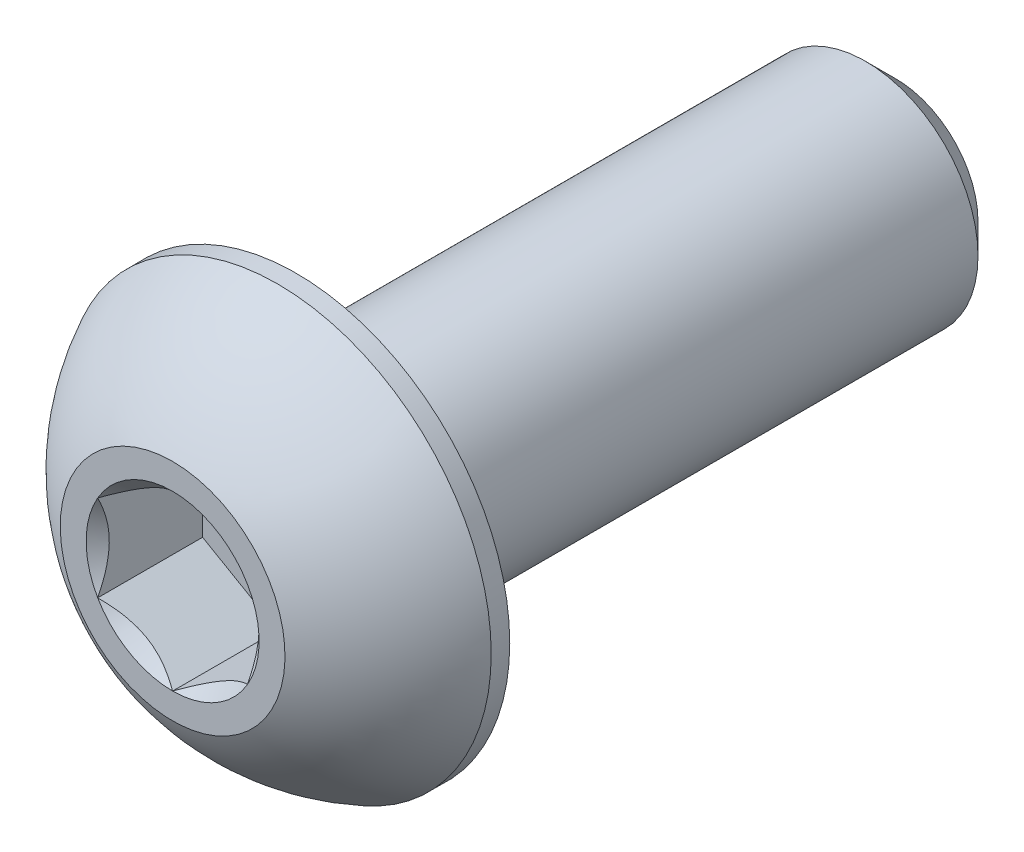
SolidWorks part; units mm, degrees
material "Alloy Steel"
ref_plane "Front Plane" through (0, 0, 0) normal (0, 0, 1) x (1, 0, 0)
ref_plane "Top Plane" through (0, 0, 0) normal (0, 1, 0) x (1, 0, 0)
ref_plane "Right Plane" through (0, 0, 0) normal (1, 0, 0) x (0, 0, -1)
sketch "Sketch1" plane through (0, 0, 0) normal (1, 0, 0) x (0, 0, -1)
  line L0 (-4.825, 0) -> (4.825, 0) construction
  line L1 (-3.175, 2.85) -> (-3.175, -2.85) construction
  line L2 (4.825, 1.5) -> (4.825, -1.5) construction
  line L3 (4.7937, 1.5541) -> (5.0437, 1.1211) construction
  line L4 (5.0437, 1.1211) -> (5.2938, 1.5541) construction
  line L5 (5.2938, 1.5541) -> (4.7937, 1.5541) construction
  line L6 (4.825, 1.5) -> (5.2625, 1.5) construction
  line L7 (5.0437, 1.5541) -> (5.0437, 1.5) construction
  line L8 (5.0437, 1.5) -> (5.0437, 1.1752) construction
  line L9 (5.0437, 1.1752) -> (5.0437, 1.1211) construction
  line L10 (5.0125, 1.1752) -> (5.075, 1.1752)
  line L11 (4.8094, 1.5271) -> (5.2781, 1.5271)
  line L12 (5.075, 1.1752) -> (5.2781, 1.5271)
  line L13 (5.0125, 1.1752) -> (4.8094, 1.5271)
  line L14 (-4.825, 1) -> (-4.825, -1) construction
  line L15 (4.825, 1.5) -> (-3.175, 1.5) construction
  point P3 (-3.175, 0)
  point P6 (-3.425, 0)
  point P21 (5.0437, 1.5271)
  point P24 (-3.4225, 2.85)
  point P25 (3.575, -1.5)
  point P26 (-4.825, 1.5)
  dimension "Head Height" = 1.65
  dimension "Length" = 8
  dimension "Head Dia" = 5.7
  dimension "Thread Dia" = 3
  dimension "Pitch" = 0.5
  dimension "D2" = 0.0625
  dimension "Drive Size" = 2
  dimension "D1" = 1.4
  dimension "D3" = 0.2475
  dimension "D4" = 1.25
sketch "Sketch2" plane through (0, 0, 0) normal (1, 0, 0) x (0, 0, -1)
  line L0 (-4.825, 0) -> (4.825, 0)
  line L1 (4.825, 0) -> (4.825, 1.1)
  line L2 (4.825, 1.5) -> (4.825, -1.5) construction
  line L3 (4.825, 1.1) -> (4.425, 1.5)
  line L4 (4.425, 1.5) -> (-3.175, 1.5)
  line L5 (-3.175, 2.85) -> (-3.175, -2.85) construction
  line L6 (-3.175, 1.5) -> (-3.175, 2.85)
  line L7 (-3.175, 2.85) -> (-3.4225, 2.85)
  line L8 (4.825, 1.5) -> (5.2625, 1.5) construction
  line L9 (-4.825, 0) -> (-4.825, 1.5)
  arc A0 (-4.825, 1.5) -> (-3.4225, 2.85) centre (-2.0302, 0) cw
  dimension "D1" = 0.4
  dimension "D2" = 45
revolve "Revolve1" add sketch "Sketch2" angle 360 about L0
sketch "Sketch3" plane through (0, 0, 4.825) normal (0, 0, 1) x (1, 0, 0)
  line L1 (0, 1.1547) -> (-1, 0.5774)
  line L2 (-1, 0.5774) -> (-1, -0.5774)
  line L3 (-1, -0.5774) -> (0, -1.1547)
  line L4 (0, -1.1547) -> (1, -0.5774)
  line L5 (1, -0.5774) -> (1, 0.5774)
  line L6 (1, 0.5774) -> (0, 1.1547)
  circle A0 centre (0, 0) radius 1 construction
  dimension "D1" = 2
extrude "Cut-Extrude1" cut sketch "Sketch3" against normal up to vertex (1.4 mm away) up to point (0, 0, 3.425)
sketch "Sketch4" plane through (0, 0, 4.825) normal (0, 0, 1) x (1, 0, 0)
  circle A0 centre (0, 0) radius 1.1547
extrude "Cut-Extrude2" cut sketch "Sketch4" against normal blind 10 draft 45
split "Split1" [suppressed] bodies to split 106
sketch "Sketch5" [suppressed] plane through (0, 0, -4.825) normal (0, 0, -1) x (-1, 0, 0)
  circle A0 centre (0, 0) radius 1.5 construction
  circle A1 centre (0, 0) radius 1.5
curve "Helix/Spiral1" [suppressed] pitch 0.5 height 8.5 turns 17
sketch "Sketch6" [suppressed] plane through (0, 0, 0) normal (1, 0, 0) x (0, 0, -1)
  line L0 (5.0125, 1.1752) -> (5.075, 1.1752) construction
  line L1 (5.0125, 1.1752) -> (4.8094, 1.5271) construction
  line L2 (4.8094, 1.5271) -> (5.2781, 1.5271) construction
  line L3 (5.075, 1.1752) -> (5.2781, 1.5271) construction
  line L4 (5.0125, 1.1752) -> (5.075, 1.1752)
  line L5 (5.0125, 1.1752) -> (4.8094, 1.5271)
  line L6 (4.8094, 1.5271) -> (5.2781, 1.5271)
  line L7 (5.075, 1.1752) -> (5.2781, 1.5271)
sweep "Cut-Sweep1" [suppressed] cut profiles "Sketch6" path "Helix/Spiral1"
sketch "Sketch7" [suppressed] plane through (0, 0, 3.175) normal (0, 0, -1) x (-1, 0, 0)
  circle A1 centre (0, 0) radius 1.5
  circle A2 centre (0, 0) radius 1.5
  dimension "D1" = 0
extrude "Boss-Extrude1" [suppressed] add sketch "Sketch7" along normal blind 10 draft 30
equation "\"D2@Sketch1\" = \"Pitch@Sketch1\" / 8"
equation "\"D1@Sketch1\"=\"Drive Size@Sketch1\"*.7"
equation "\"D3@Sketch1\"=\"Head Height@Sketch1\"*.15"
equation "\"D1@Sketch2\"=\"Pitch@Sketch1\"*.8"
equation "\"D1@Sketch3\"=\"Drive Size@Sketch1\""
equation "\"D4@Helix/Spiral1\"=\"Pitch@Sketch1\""
equation "\"D3@Helix/Spiral1\"=\"Length@Sketch1\"+\"Pitch@Sketch1\""
equation "\"D4@Sketch1\"=\"Pitch@Sketch1\"*2.5"
